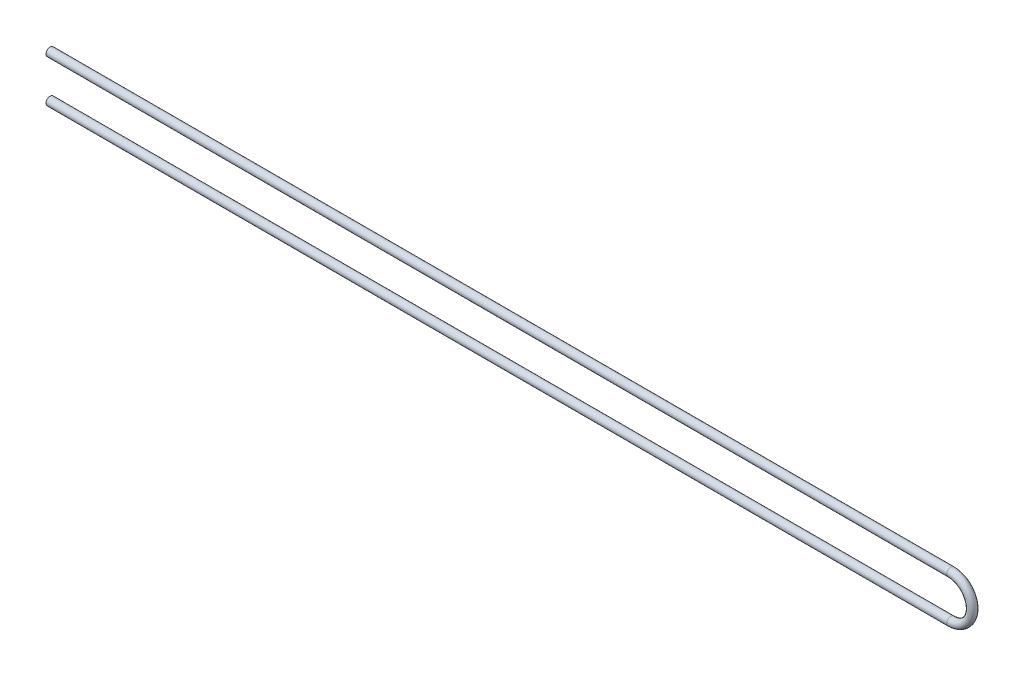
SolidWorks part; units mm, degrees
ref_plane "Front Plane" through (0, 0, 0) normal (0, 0, 1) x (1, 0, 0)
ref_plane "Top Plane" through (0, 0, 0) normal (0, 1, 0) x (1, 0, 0)
ref_plane "Right Plane" through (0, 0, 0) normal (1, 0, 0) x (0, 0, -1)
sketch "Sketch1" plane through (0, 0, 0) normal (0, 0, 1) x (1, 0, 0)
  line L0 (0, 0) -> (2325, 0)
  line L1 (2325, -110) -> (0, -110)
  arc A0 (2325, 0) -> (2325, -110) centre (2325, -55) cw
  dimension "D1" = 2325
  dimension "D2" = 55
sweep "Sweep-Thin1" add path "Sketch1" circular profile diameter 21.3 parameters "D1"=0.5, "D3"=21.3
